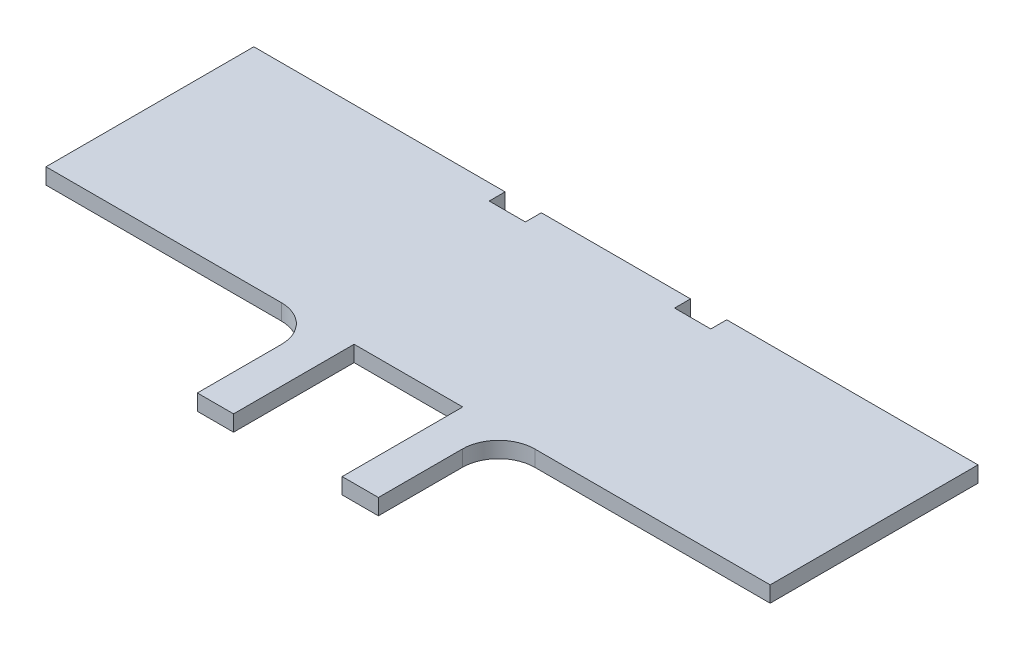
SolidWorks part; units mm, degrees
ref_plane "Front Plane" through (0, 0, 0) normal (0, 0, 1) x (1, 0, 0)
ref_plane "Top Plane" through (0, 0, 0) normal (0, 1, 0) x (1, 0, 0)
ref_plane "Right Plane" through (0, 0, 0) normal (1, 0, 0) x (0, 0, -1)
sketch "Sketch1" plane through (0, 0, 0) normal (0, 1, 0) x (1, 0, 0)
  line L0 (-127, 26.1308) -> (127, 26.1308) construction
  line L2 (-127, -40.9252) -> (-127, 31.9728)
  line L3 (-127, 31.9728) -> (-38.862, 31.9728)
  line L4 (127, -40.9252) -> (127, 31.9728)
  line L7 (-127, -40.9252) -> (127, -40.9252) construction
  line L10 (-31.75, -83.0892) -> (-19.05, -83.0892)
  line L12 (0, -40.8024) -> (19.05, -40.8024)
  line L13 (19.05, -40.8024) -> (19.05, -83.0892)
  line L14 (0, -40.8024) -> (-19.05, -40.8024)
  line L15 (-19.05, -40.8024) -> (-19.05, -83.0892)
  line L16 (19.05, -83.0892) -> (31.75, -83.0892)
  line L17 (-127, -40.9252) -> (-44.45, -40.9252)
  line L18 (-31.75, -53.6252) -> (-31.75, -83.0892)
  line L19 (127, -40.9252) -> (44.45, -40.9252)
  line L20 (31.75, -53.6252) -> (31.75, -83.0892)
  line L27 (-26.162, 31.9728) -> (26.162, 31.9728)
  line L28 (38.862, 31.9728) -> (127, 31.9728)
  line L29 (-38.862, 31.9728) -> (-38.862, 26.3848)
  line L30 (-38.862, 26.3848) -> (-26.162, 26.3848)
  line L31 (-26.162, 26.3848) -> (-26.162, 31.9728)
  line L32 (26.162, 31.9728) -> (26.162, 26.3848)
  line L33 (26.162, 26.3848) -> (38.862, 26.3848)
  line L34 (38.862, 26.3848) -> (38.862, 31.9728)
  arc A0 (44.45, -40.9252) -> (31.75, -53.6252) centre (44.45, -53.6252) ccw
  arc A1 (-31.75, -53.6252) -> (-44.45, -40.9252) centre (-44.45, -53.6252) ccw
  point P0 (0, 0)
  point P10 (0, -41.181)
  point P27 (-31.75, -40.9252)
  dimension "D6" = 12.7
  dimension "D2" = 254
  dimension "D3" = 5.842
  dimension "D4" = 67.056
  dimension "D5" = 19.05
  dimension "D7" = 12.7
  dimension "D8" = 72.898
  dimension "D9" = 12.7
  dimension "D10" = 88.138
  dimension "D11" = 5.588
  dimension "D12" = 12.7
  dimension "D13" = 29.464
  dimension "D14" = 42.2868
extrude "Boss-Extrude1" add sketch "Sketch1" along normal blind 5.588
